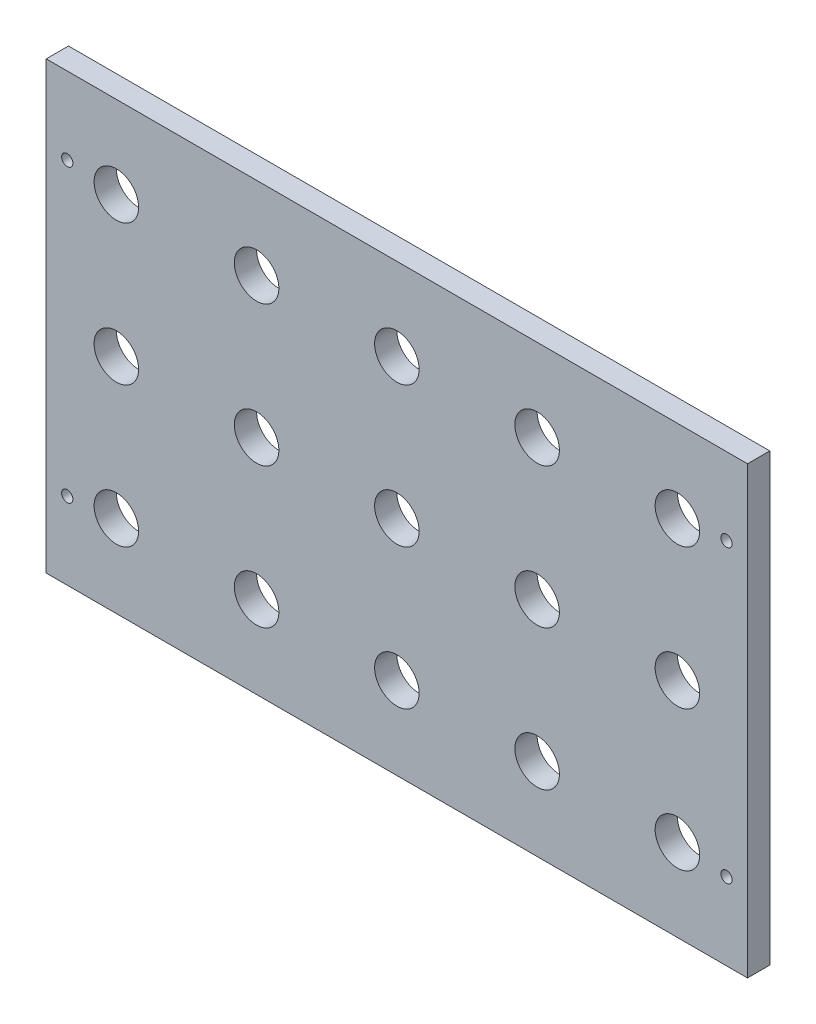
SolidWorks part; units mm, degrees
ref_plane "Front Plane" through (0, 0, 0) normal (0, 0, 1) x (1, 0, 0)
ref_plane "Top Plane" through (0, 0, 0) normal (0, 1, 0) x (1, 0, 0)
ref_plane "Right Plane" through (0, 0, 0) normal (1, 0, 0) x (0, 0, -1)
sketch "Sketch1" plane through (0, 0, 0) normal (0, 0, 1) x (1, 0, 0)
  line L1 (0, 0) -> (200, 0)
  line L2 (0, 0) -> (0, 127)
  line L3 (0, 127) -> (200, 127)
  line L4 (200, 0) -> (200, 127)
  circle A3 centre (6, 105) radius 1.6
  circle A4 centre (6, 22) radius 1.6
  circle A5 centre (194, 22) radius 1.6
  circle A6 centre (194, 105) radius 1.6
  dimension "D11" = 3.2
  dimension "D14" = 3.2
  dimension "D17" = 3.2
  dimension "D22" = 3.2
  dimension "D1" = 127
  dimension "D2" = 200
  dimension "D12" = 6
  dimension "D13" = 22
  dimension "D15" = 6
  dimension "D16" = 22
  dimension "D18" = 6
  dimension "D19" = 22
  dimension "D20" = 6
  dimension "D21" = 22
extrude "Wall" add sketch "Sketch1" along normal blind 6.35
sketch "Sketch2" plane through (0, 0, 6.35) normal (0, 0, 1) x (1, 0, 0)
  line L0 (100, 127) -> (100, 98.425) construction
  line L1 (200, 127) -> (0, 127) construction
  line L2 (100, 98.425) -> (66.6667, 98.425) construction
  line L3 (100, 98.425) -> (133.3333, 98.425) construction
  line L4 (0, 127) -> (0, 0) construction
  circle A0 centre (100, 98.425) radius 3.9687
  circle A1 centre (66.6667, 98.425) radius 3.9688
  circle A2 centre (133.3333, 98.425) radius 3.9687
  dimension "D2" = 7.9375
  dimension "D1" = 28.575
  dimension "D3" = 66.6667
extrude "RodSupportCutouts" [suppressed] cut sketch "Sketch2" against normal up to next
sketch "Sketch3" plane through (0, 0, 6.35) normal (0, 0, 1) x (1, 0, 0)
  line L1 (25.4, 88.9) -> (174.6, 88.9)
  line L2 (25.4, 88.9) -> (25.4, 114.3)
  line L3 (25.4, 114.3) -> (174.6, 114.3)
  line L4 (174.6, 88.9) -> (174.6, 114.3)
  line L5 (25.4, 88.9) -> (174.6, 114.3) construction
  line L6 (25.4, 114.3) -> (174.6, 88.9) construction
  line L7 (200, 127) -> (0, 127) construction
  line L8 (0, 127) -> (0, 0) construction
  point P0 (100, 101.6)
  point P9 (100, 127)
  dimension "D1" = 25.4
  dimension "D2" = 25.4
  dimension "D3" = 25.4
extrude "CannulaLargeCutout" [suppressed] cut sketch "Sketch3" against normal up to next
sketch "Sketch4" plane through (0, 0, 6.35) normal (0, 0, 1) x (1, 0, 0)
  line L0 (6, 103.5) -> (194, 103.5) construction
  line L1 (6, 105) -> (6, 22) construction
  line L2 (194, 105) -> (194, 22) construction
  line L3 (200, 127) -> (0, 127) construction
  line L4 (0, 127) -> (0, 0) construction
  circle A0 centre (60, 103.5) radius 6.35
  circle A1 centre (20, 103.5) radius 6.35
  circle A2 centre (100, 103.5) radius 6.35
  circle A3 centre (140, 103.5) radius 6.35
  circle A4 centre (60, 63.5) radius 6.35
  circle A5 centre (100, 63.5) radius 6.35
  circle A6 centre (140, 63.5) radius 6.35
  circle A7 centre (60, 23.5) radius 6.35
  circle A8 centre (100, 23.5) radius 6.35
  circle A9 centre (140, 23.5) radius 6.35
  circle A10 centre (20, 63.5) radius 6.35
  circle A11 centre (20, 23.5) radius 6.35
  circle A12 centre (180, 103.5) radius 6.35
  circle A13 centre (180, 63.5) radius 6.35
  circle A14 centre (180, 23.5) radius 6.35
  point P42 (100, 127)
  point P45 (0, 63.5)
  dimension "D3" = 12.7
  dimension "D1" = 5
  dimension "D2" = 3
extrude "CannulaHoles" cut sketch "Sketch4" against normal up to next
equation "\"Length\"= 283mm"
equation "\"Width\"= 225mm"
equation "\"WallThickness\"= 12.5mm"
equation "\"UpperWaterJacketThickness\"= 28mm"
equation "\"SpacerHeight\"= 80.2mm"
equation "\"SpacerCornerWidth\"= 10mm"
equation "\"SpacerCornerHeight\"= 60.16mm"
equation "\"SpacerPegDiameter\"= 10mm"
equation "\"SpacerPegHeight\"= 10mm"
equation "\"TubingShort\"= 110mm"
equation "\"TubingLong\"= 175mm"
equation "\"PlateLength\"= 252mm"
equation "\"PlateWidth\"= 190mm"
equation "\"PlateHoleDiameter\"= 5.9mm"
equation "\"PlateHoleBottom\"= 2mm"
equation "\"PlateHoleSide\"= 1.55mm"
equation "\"PlateHoleSpacing\"= 3.1mm"
equation "\"PlateThickness\"= 1.55mm"
equation "\"ReservoirBottom\"= 12.5mm"
equation "\"ReservoirSupportWidth\"= 12mm"
equation "\"ReservoirSupportHeight\"= 15.1mm"
equation "\"ReservoirSupportPlacementHeight\"= 50mm"
equation "\"ReservoirHoleDiameter\"= 12.7mm"
equation "\"ReservoirHoleRight\"= 25mm"
equation "\"ReservoirHoleTop\"= \"ReservoirSupportPlacementHeight\""
equation "\"ReservoirHeight\"= 90mm"
equation "\"ReservoirPortBottom\"= 4mm"
equation "\"ReservoirPortTop\"= 10mm"
equation "\"ReservoirPortWidth\"= 101mm"
equation "\"CustomSpacerWallThickness\"= 0.25in"
equation "\"CustomSpacerHeight\"= 5in"
equation "\"CustomSpacerRodHoleHeight\"= .75in"
equation "\"CustomSpacerRodHoleDiameter\"= .3125in"
equation "\"ScrewBlockSide\"= 12mm"
equation "\"ScrewBlockUpperHeight\"= 16mm"
equation "\"ScrewBlockLowerHeight\"= 16mm"
equation "\"InternalLength\"= \"Length\" - ( 2 * \"WallThickness\" )"
equation "\"InternalWidth\"= \"Width\" - ( 2 * \"WallThickness\" )"
equation "\"CustomSpacerPegHeight\"= 1in"
equation "\"CustomSpacerScrewBore\"=3.2mm"
equation "\"CustomSpacerScrewDepth\"=10mm"
equation "\"D1@Sketch1\"=\"CustomSpacerHeight\""
equation "\"D2@Sketch1\"=\"InternalWidth\""
equation "\"D11@Sketch1\"=\"CustomSpacerScrewBore\""
equation "\"D12@Sketch1\"=\"ScrewBlockSide\"/2"
equation "\"D13@Sketch1\"=\"ScrewBlockUpperHeight\"+\"ScrewBlockSide\"/2"
equation "\"D14@Sketch1\"=\"CustomSpacerScrewBore\""
equation "\"D15@Sketch1\"=\"ScrewBlockSide\"/2"
equation "\"D16@Sketch1\"=\"ScrewBlockLowerHeight\"+\"ScrewBlockSide\"/2"
equation "\"D17@Sketch1\"=\"CustomSpacerScrewBore\""
equation "\"D18@Sketch1\"=\"ScrewBlockSide\"/2"
equation "\"D19@Sketch1\"=\"ScrewBlockUpperHeight\"+\"ScrewBlockSide\"/2"
equation "\"D20@Sketch1\"=\"ScrewBlockSide\"/2"
equation "\"D21@Sketch1\"=\"ScrewBlockLowerHeight\"+\"ScrewBlockSide\"/2"
equation "\"D22@Sketch1\"=\"CustomSpacerScrewBore\""
equation "\"D1@Wall\" = \"CustomSpacerWallThickness\""
equation "\"D1@Sketch2\"=\"CustomSpacerRodHoleHeight\" + \"CustomSpacerRodHoleDiameter\" +0.0625in"
equation "\"D2@Sketch2\"=\"CustomSpacerRodHoleDiameter\""
equation "\"D3@Sketch2\"=\"InternalWidth\" / 3"
equation "\"D1@Sketch3\"=1in"
